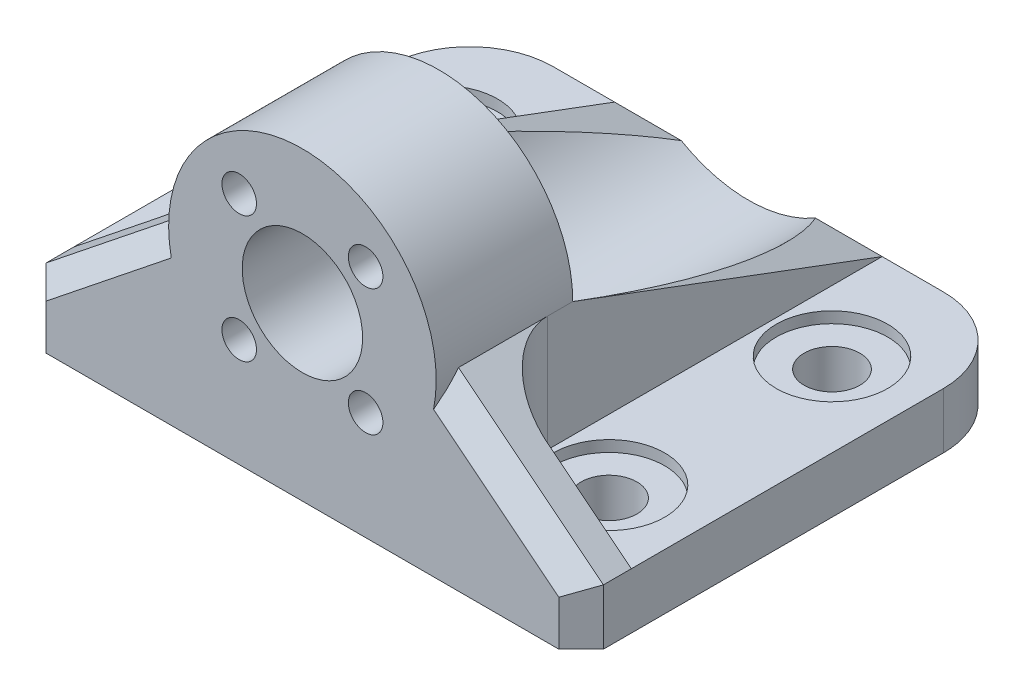
SolidWorks part; units mm, degrees
ref_plane "Front Plane" through (0, 0, 0) normal (0, 0, 1) x (1, 0, 0)
ref_plane "Top Plane" through (0, 0, 0) normal (0, 1, 0) x (1, 0, 0)
ref_plane "Right Plane" through (0, 0, 0) normal (1, 0, 0) x (0, 0, -1)
sketch "Sketch1" plane through (0, 0, 0) normal (0, 1, 0) x (1, 0, 0)
  line L0 (0, 2) -> (2, 0)
  line L1 (2, 0) -> (48, 0)
  line L2 (0, 2) -> (0, 32.5)
  line L3 (7.5, 40) -> (42.5, 40)
  line L4 (50, 2) -> (50, 32.5)
  line L5 (48, 0) -> (50, 2)
  arc A0 (42.5, 40) -> (50, 32.5) centre (42.5, 32.5) cw
  arc A1 (0, 32.5) -> (7.5, 40) centre (7.5, 32.5) cw
  point P0 (0, 0)
  point P3 (50, 0)
  point P7 (50, 40)
  point P10 (0, 40)
  dimension "D3" = 7.5
  dimension "D1" = 50
  dimension "D2" = 40
extrude "Boss-Extrude1" add sketch "Sketch1" along normal blind 5
sketch "Sketch2" plane through (0, 0, 0) normal (0, 0, 1) x (1, 0, 0)
  line L0 (2, 0) -> (48, 0) construction
  line L1 (25, 15.38) -> (30.4, 15.38) construction
  line L2 (25, 15.38) -> (25, 20.78) construction
  circle A0 centre (25, 15.38) radius 12
  circle A1 centre (25, 15.38) radius 5.4
  circle A2 centre (19.33, 21.05) radius 1.55
  circle A3 centre (30.67, 21.05) radius 1.55
  circle A4 centre (30.67, 9.71) radius 1.55
  circle A5 centre (19.33, 9.71) radius 1.55
  point P5 (25, 0)
  dimension "D1" = 24
  dimension "D2" = 15.38
  dimension "D3" = 10.8
  dimension "D4" = 3.1
  dimension "D5" = 5.67
  dimension "D6" = 5.67
extrude "Boss-Extrude2" add sketch "Sketch2" against normal blind 12.25
sketch "Sketch3" plane through (0, 0, 0) normal (0, 0, 1) x (1, 0, 0)
  line L0 (13, 15.38) -> (0, 5)
  line L1 (2, 5) -> (18.9787, 5) construction
  line L2 (13, 5) -> (13, 15.38) construction
  line L3 (0, 5) -> (18.9787, 5)
  line L4 (25, 15.38) -> (25, 12.2355) construction
  line L5 (50, 5) -> (31.0213, 5)
  line L6 (37, 15.38) -> (50, 5)
  arc A0 (31.0213, 5) -> (18.9787, 5) centre (25, 15.38) ccw construction
  arc A1 (13, 15.38) -> (18.9787, 5) centre (25, 15.38) ccw
  arc A2 (37, 15.38) -> (31.0213, 5) centre (25, 15.38) cw
  dimension "D2" = 10.38
extrude "Boss-Extrude3" add sketch "Sketch3" against normal blind 4.5
chamfer "Chamfer1" distance 2 angle 45 2 edges at (43.5, 10.19, 0) (6.5, 10.19, 0)
ref_plane "Plane1" through (13, 0, 0) normal (-1, 0, 0) x (0, 0, 1)
sketch "Sketch4" plane through (13, 0, 0) normal (-1, 0, 0) x (0, 0, 1)
  line L0 (-40, 5) -> (-4.5, 5)
  line L1 (-12.25, 15.38) -> (-12.25, 5) construction
  line L2 (-12.25, 27.38) -> (-12.25, 5) construction
  line L3 (-12.25, 15.38) -> (-40, 5)
  line L4 (-12.25, 15.38) -> (-4.5, 15.38)
  line L5 (-4.5, 15.38) -> (-4.5, 5)
extrude "Boss-Extrude4" add sketch "Sketch4" against normal blind 24
sketch "Sketch5" plane through (0, 0, 0) normal (0, 0, 1) x (1, 0, 0)
  line L0 (30.4, 15.38) -> (19.6, 15.38) construction
  circle A0 centre (25, 15.38) radius 5.4
  circle A1 centre (30.67, 9.71) radius 1.55
  circle A2 centre (19.33, 9.71) radius 1.55
  dimension "D1" = 3.1
  dimension "D2" = 3.1
  dimension "D3" = 10.8
extrude "Cut-Extrude1" cut sketch "Sketch5" against normal through all
sketch "Sketch6" plane through (0, 0, -40) normal (0, 0, -1) x (-1, 0, 0)
  circle A0 centre (-25, 15.38) radius 12
extrude "Cut-Extrude2" cut sketch "Sketch6" against normal blind 27.75
fillet "Fillet1" radius 5.5 2 edges at (13, 10.19, -4.5) (37, 10.19, -4.5)
sketch "Sketch7" plane through (0, 0, 0) normal (0, -1, 0) x (1, 0, 0)
  line L0 (0, -32.5) -> (0, -2) construction
  line L1 (0, -25.5) -> (50, -25.5)
  line L2 (0, -25.5) -> (0, -32.5)
  line L3 (0.2716, -34.5) -> (49.7284, -34.5)
  line L4 (50, -25.5) -> (50, -32.5)
  line L5 (50, -2) -> (50, -32.5) construction
  line L6 (2, 0) -> (48, 0) construction
  line L7 (0, -5.5) -> (50, -5.5)
  line L8 (0, -5.5) -> (0, -14.5)
  line L9 (0, -14.5) -> (50, -14.5)
  line L10 (50, -5.5) -> (50, -14.5)
  line L11 (42.5, -40) -> (7.5, -40) construction
  arc A0 (0, -32.5) -> (7.5, -40) centre (7.5, -32.5) ccw construction
  arc A1 (42.5, -40) -> (50, -32.5) centre (42.5, -32.5) ccw construction
  arc A2 (0, -32.5) -> (0.2716, -34.5) centre (7.5, -32.5) ccw
  arc A3 (49.7284, -34.5) -> (50, -32.5) centre (42.5, -32.5) ccw
  dimension "D1" = 5.5
  dimension "D2" = 9
  dimension "D3" = 5.5
  dimension "D4" = 9
extrude "Boss-Extrude5" add sketch "Sketch7" along normal blind 1 draft 45
sketch "Sketch8" plane through (0, -1, 0) normal (0, -1, 0) x (1, 0, 0)
  line L0 (0, -20) -> (50, -20) construction
  line L1 (0, -25.5) -> (0, -14.5) construction
  line L2 (50, -14.5) -> (50, -25.5) construction
  line L3 (25, 0) -> (25, -40) construction
  line L4 (2, 0) -> (48, 0) construction
  line L5 (42.5, -40) -> (7.5, -40) construction
  line L6 (49, -26.5) -> (1, -26.5) construction
  line L7 (1, -26.5) -> (1, -32.5) construction
  circle A0 centre (7.5, -30) radius 2.5
  circle A1 centre (42.5, -30) radius 2.5
  circle A2 centre (42.5, -10) radius 2.5
  circle A3 centre (7.5, -10) radius 2.5
  dimension "D1" = 5
  dimension "D2" = 3.5
  dimension "D3" = 6.5
extrude "Cut-Extrude3" cut sketch "Sketch8" against normal through all
sketch "Sketch9" plane through (0, 5, 0) normal (0, 1, 0) x (1, 0, 0)
  circle A0 centre (7.5, 30) radius 5
  circle A1 centre (7.5, 10) radius 5
  circle A2 centre (42.5, 30) radius 5
  circle A3 centre (42.5, 10) radius 5
  dimension "D1" = 10
  dimension "D2" = 10
  dimension "D3" = 10
  dimension "D4" = 10
extrude "Cut-Extrude4" cut sketch "Sketch9" against normal blind 1
